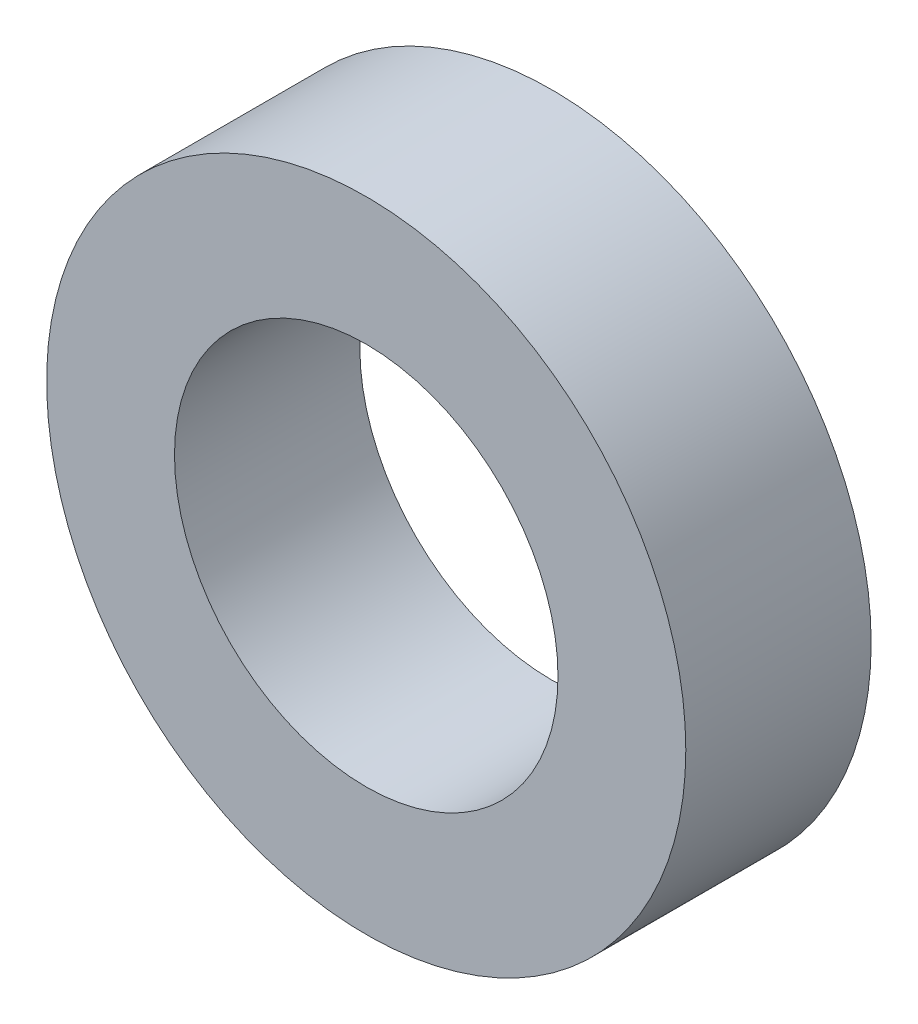
SolidWorks part; units mm, degrees
material "Acrylic (Medium-high impact)"
ref_plane "Front Plane" through (0, 0, 0) normal (0, 0, 1) x (1, 0, 0)
ref_plane "Top Plane" through (0, 0, 0) normal (0, 1, 0) x (1, 0, 0)
ref_plane "Right Plane" through (0, 0, 0) normal (1, 0, 0) x (0, 0, -1)
sketch "Sketch1" plane through (0, 0, 0) normal (0, 0, 1) x (1, 0, 0)
  circle A0 centre (0, 0) radius 3
  circle A1 centre (0, 0) radius 5
  dimension "D1" = 6
  dimension "D2" = 10
extrude "Boss-Extrude1" add sketch "Sketch1" along normal blind 2.9
equation "\"smallPulleyTeeth\"= 15"
equation "\"largePulleyTeeth\"= 30"
equation "\"eighthThick\"= 2.9mm"
equation "\"sixteenthThick\" = 1.7mm"
equation "\"quarterThick\"=6.0mm"
equation "\"OD\" = 146mm"
equation "\"puckAngle\" = 60.5deg"
equation "\"puckDiam\" = 76.5mm"
equation "\"axlePress\" = 5.9mm"
equation "\"press\" = 0.2mm"
equation "\"wheelClear\" = 0.3mm"
equation "\"10-32clear\" = 4.8mm"
equation "\"6-32clear\" = 3.3mm"
equation "\"8-32clear\" = 4.0mm"
equation "\"D1@Boss-Extrude1\"=\"eighthThick\""
